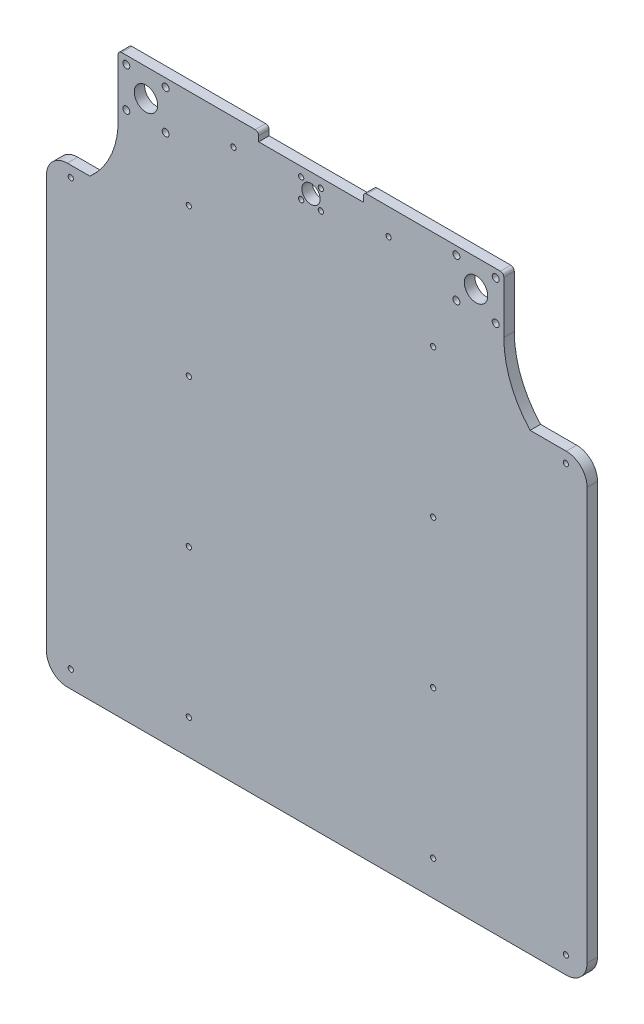
SolidWorks part; units mm, degrees
ref_plane "Alzado" through (0, 0, 0) normal (0, 0, 1) x (1, 0, 0)
ref_plane "Planta" through (0, 0, 0) normal (0, 1, 0) x (1, 0, 0)
ref_plane "Vista lateral" through (0, 0, 0) normal (1, 0, 0) x (0, 0, -1)
sketch "Croquis1" plane through (0, 0, 0) normal (0, 0, 1) x (1, 0, 0)
  line L0 (32.1154, 16) -> (87.6356, 16)
  line L1 (-109, 16) -> (-87.6356, 16)
  line L2 (-111, 14) -> (-111, -16.0875)
  line L3 (-135.2776, -316) -> (-119.3643, -316)
  line L4 (-87.6356, 16) -> (-44.6644, 16)
  line L5 (30.1154, 14) -> (30.1154, 10.91)
  line L6 (0, 0) -> (0, 78.8056) construction
  line L7 (30.1154, 10.91) -> (-30.1154, 10.91)
  line L8 (-111, 0) -> (-111, -16)
  line L9 (-111, -16) -> (-111, 16)
  line L10 (-44.6644, 16) -> (-32.1154, 16)
  line L11 (-119.3643, -316) -> (119.3644, -316)
  line L12 (111, 14) -> (111, -16.0875)
  line L13 (109, 16) -> (87.6356, 16)
  line L14 (-30.1154, 14) -> (-30.1154, 10.91)
  line L15 (-8.3, -8.3) -> (8.3, 8.3) construction
  line L16 (-127.2776, -54.7893) -> (126.134, -54.7893) construction
  line L17 (-96, -316) -> (-44.6644, -316)
  line L18 (119.3644, -316) -> (130.2951, -316)
  line L19 (-8.3, 8.3) -> (8.3, -8.3) construction
  line L20 (-127.2776, -54.7893) -> (-135.2776, -54.7893)
  line L21 (-111, 16) -> (-79, -16) construction
  line L22 (-111, -16) -> (-79, 16) construction
  line L23 (-135.2776, -54.7893) -> (-140.2776, -54.7893)
  line L24 (-138.2776, -61) -> (-136.7776, -61) construction
  line L26 (-135.2776, -316) -> (-140.2776, -316)
  line L27 (-152.2776, -66.7893) -> (-152.2776, -304)
  line L29 (130.2951, -316) -> (146.9429, -316)
  line L30 (158.9429, -70.8585) -> (158.9429, -304)
  line L31 (145.2224, -61) -> (146.7224, -61) construction
  line L32 (126.134, -54.7893) -> (146.9429, -54.7893)
  line L35 (158.9429, -66.7893) -> (158.9429, -70.8585)
  circle A0 centre (0, 0) radius 5.25
  circle A1 centre (-95, 0) radius 6.75
  circle A2 centre (95, 0) radius 6.75
  circle A3 centre (146.7224, -61) radius 1.5
  circle A4 centre (-83.6863, 11.3137) radius 2
  circle A5 centre (-106.3137, 11.3137) radius 2
  circle A6 centre (-83.6863, -11.3137) radius 2
  circle A7 centre (-106.3137, -11.3137) radius 2
  circle A8 centre (106.3137, -11.3137) radius 2
  circle A9 centre (83.6863, -11.3137) radius 2
  circle A10 centre (83.6863, 11.3137) radius 2
  arc A11 (-111, -16.0875) -> (-127.2776, -54.7893) centre (-158.9474, -18.6953) cw
  arc A12 (111, -16.0875) -> (126.134, -54.7893) centre (168.0523, -16.0875) ccw
  arc A13 (-140.2776, -316) -> (-152.2776, -304) centre (-140.2776, -304) cw
  arc A14 (158.9429, -304) -> (146.9429, -316) centre (146.9429, -304) cw
  arc A15 (158.9429, -66.7893) -> (146.9429, -54.7893) centre (146.9429, -66.7893) ccw
  circle A16 centre (5.6569, 5.6569) radius 1.5
  circle A17 centre (-5.6569, 5.6569) radius 1.5
  circle A18 centre (-5.6569, -5.6569) radius 1.5
  circle A19 centre (5.6569, -5.6569) radius 1.5
  arc A20 (-140.2776, -54.7893) -> (-152.2776, -66.7893) centre (-140.2776, -66.7893) ccw
  circle A21 centre (146.7224, -306) radius 1.5
  circle A22 centre (-138.2776, -306) radius 1.5
  circle A23 centre (-138.2776, -61) radius 1.5
  circle A24 centre (-70.3321, -41) radius 1.5
  circle A25 centre (-70.3321, -126) radius 1.5
  circle A26 centre (-70.3321, -211) radius 1.5
  circle A27 centre (-70.3321, -296) radius 1.5
  circle A28 centre (-44.6644, 1) radius 1.5
  arc A29 (109, 16) -> (111, 14) centre (109, 14) cw
  arc A30 (-111, 14) -> (-109, 16) centre (-109, 14) cw
  circle A31 centre (70.3321, -296) radius 1.5
  circle A32 centre (70.3321, -211) radius 1.5
  circle A33 centre (70.3321, -126) radius 1.5
  circle A34 centre (70.3321, -41) radius 1.5
  arc A35 (-32.1154, 16) -> (-30.1154, 14) centre (-32.1154, 14) cw
  circle A36 centre (44.6644, 1) radius 1.5
  circle A37 centre (106.3137, 11.3137) radius 2
  arc A38 (30.1154, 14) -> (32.1154, 16) centre (32.1154, 14) cw
  point P71 (0, 16)
  point P98 (111, 16)
  point P101 (-111, 16)
  point P106 (30.1154, 16)
  point P108 (-147.2776, -54.7893)
  dimension "D3" = 285
  dimension "D4" = 12
  dimension "D5" = 10.5
  dimension "D6" = 14
  dimension "D7" = 285
  dimension "D8" = 13.5
  dimension "D9" = 245
  dimension "D10" = 4
  dimension "D11" = 222
  dimension "D12" = 85
  dimension "D13" = 85
  dimension "D16" = 190
  dimension "D2" = 13.5
  dimension "D18" = 14
  dimension "D21" = 4
  dimension "D19" = 4
  dimension "D20" = 4
  dimension "D22" = 2
  dimension "D24" = 12
  dimension "D25" = 12
  dimension "D14" = 85
  dimension "D15" = 20
  dimension "D17" = 95
  dimension "D23" = 20
extrude "Saliente-Extruir1" add sketch "Croquis1" along normal blind 6 contours L11 L12 L13 L10 L4 L1 L2 A11 A36 A33 A31 A28 A27 A26 A25 A24 A23 A22 A21 A19 A18 A17 A16 A9 region at (2.8125, -159.4344, 0)
